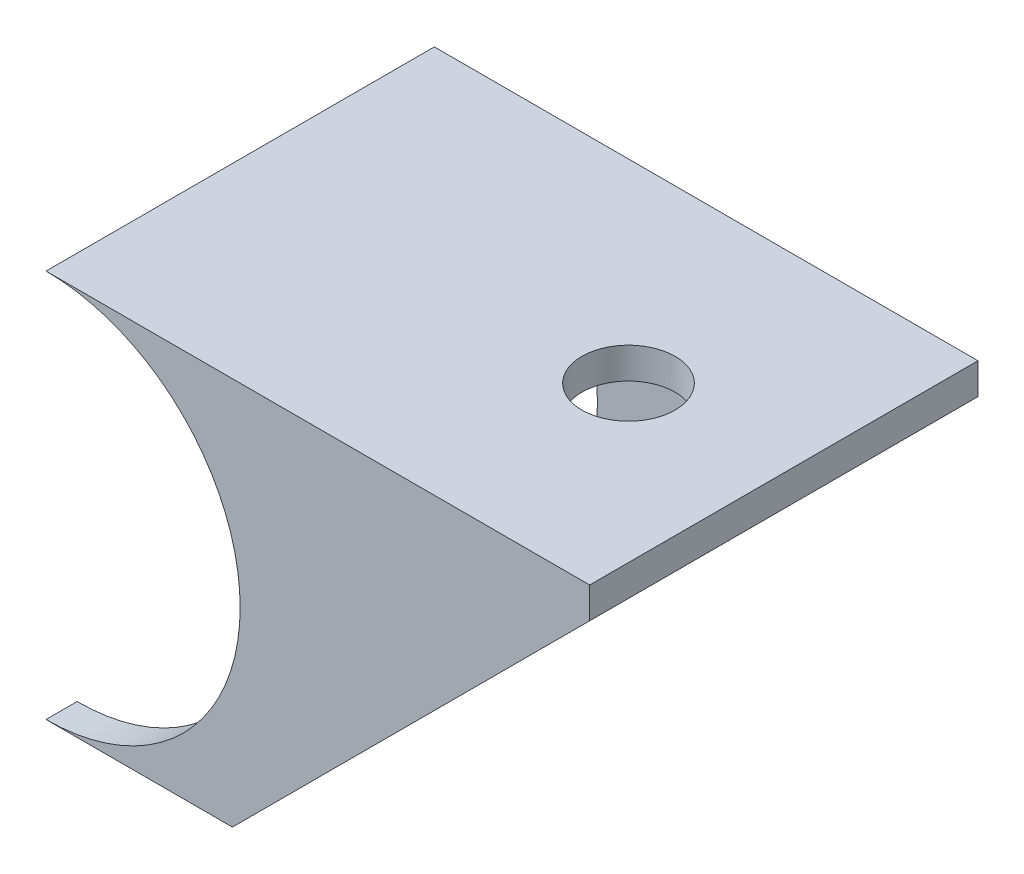
SolidWorks part; units mm, degrees
material "AISI 4130 Stal normalizowana w 870C"
ref_plane "Płaszczyzna XY" through (0, 0, 0) normal (0, 0, 1) x (1, 0, 0)
ref_plane "Płaszczyzna XZ" through (0, 0, 0) normal (0, 1, 0) x (1, 0, 0)
ref_plane "Płaszczyzna YZ" through (0, 0, 0) normal (1, 0, 0) x (0, 0, -1)
sketch "Szkic1" plane through (0, 0, 0) normal (0, 0, 1) x (1, 0, 0)
  line L0 (20, 12.2857) -> (-3, -10.7143)
  line L1 (-15, -10.7143) -> (-3, -10.7143)
  line L3 (-15, 14.2857) -> (20, 14.2857)
  line L4 (20, 12.2857) -> (20, 14.2857)
  line L5 (-15, -10.7143) -> (20, 14.2857) construction
  line L6 (-15, 14.2857) -> (19.1575, -18.2453) construction
  arc A0 (-15, -10.7143) -> (-15, 14.2857) centre (-15, 1.7857) ccw
  point P0 (0, 0)
  dimension "D1" = 25
  dimension "D2" = 35
  dimension "D3" = 12.5
  dimension "D4" = 0
  dimension "D5" = 2
  dimension "D6" = 45
  dimension "D7" = 20
extrude "Dodanie-wyciągnięcie1" add sketch "Szkic1" along normal mid plane 25
shell "Skorupa2" thickness 2 removed face at (-9, -10.7143, 0) removed face at (8.5, 0.7857, 0) removed face at (-8.75, 1.7857, 0) removed face at (20, 13.2857, 0)
sketch "Szkic2" plane through (0, 14.2857, 0) normal (0, 1, 0) x (1, 0, 0)
  line L0 (20, -12.5) -> (20, 12.5) construction
  circle A0 centre (10, 0) radius 3
  circle A1 centre (8, -24.9199) radius 4
  dimension "D2" = 25
  dimension "D3" = 10
  dimension "D4" = 6
  dimension "D5" = 8
  dimension "D6" = 12
  dimension "D1" = 0
extrude "Wytnij-wyciągnięcie1" cut sketch "Szkic2" against normal blind 60
